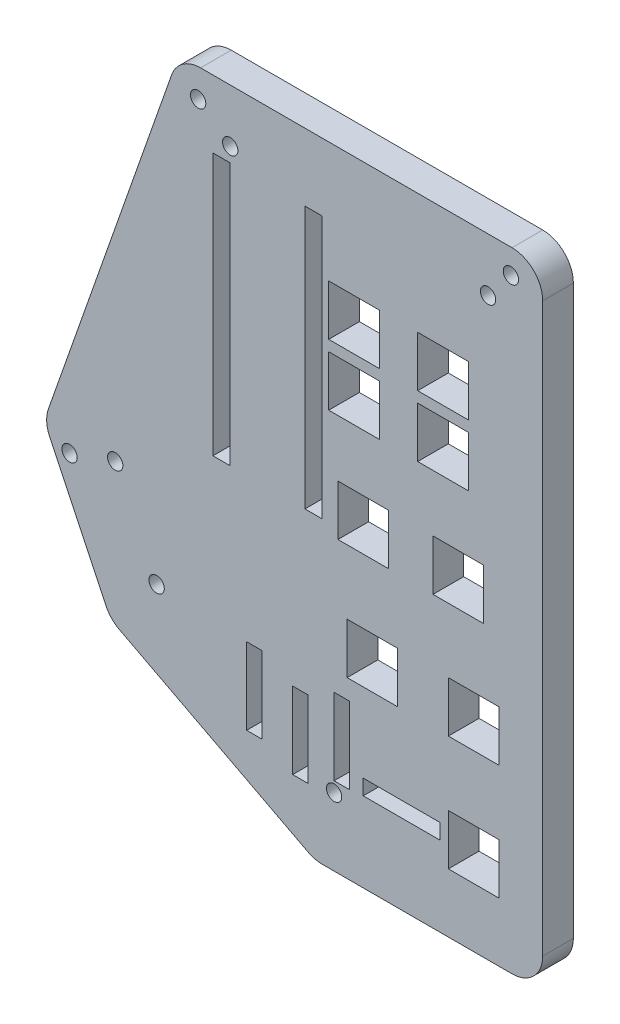
SolidWorks part; units mm, degrees
ref_plane "Front Plane" through (0, 0, 0) normal (0, 0, 1) x (1, 0, 0)
ref_plane "Top Plane" through (0, 0, 0) normal (0, 1, 0) x (1, 0, 0)
ref_plane "Right Plane" through (0, 0, 0) normal (1, 0, 0) x (0, 0, -1)
sketch "Sketch1" plane through (0, 0, 0) normal (0, 0, 1) x (1, 0, 0)
  line L6 (-20.066, -57.15) -> (46.99, -57.15) construction
  line L7 (-12.446, -73.152) -> (46.99, -73.152) construction
  line L8 (-3.3141, 6.35) -> (48.26, 6.35)
  line L9 (53.34, 1.27) -> (53.34, -92.71)
  line L10 (48.26, -97.79) -> (16.847, -97.79)
  line L16 (-8.1072, 2.9529) -> (-28.5162, -55.1739)
  line L18 (-20.066, -57.15) -> (-29.21, -57.15) construction
  line L26 (0, 0) -> (46.99, 0) construction
  line L27 (46.99, 0) -> (46.99, -88.9) construction
  line L28 (46.99, -88.9) -> (17.78, -88.9) construction
  line L29 (17.78, -88.9) -> (-12.446, -73.152) construction
  line L30 (-12.446, -73.152) -> (-20.066, -57.15) construction
  line L31 (-20.066, -57.15) -> (0, 0) construction
  line L32 (46.99, -57.15) -> (46.99, -88.9) construction
  line L33 (17.78, -88.9) -> (15.603, -97.79) construction
  line L34 (-12.446, -73.152) -> (-17.9301, -78.4424) construction
  line L35 (14.4997, -97.2152) -> (-16.7505, -80.9336)
  line L36 (-28.3096, -59.0409) -> (-18.9898, -78.6124)
  arc A0 (14.4997, -97.2152) -> (16.847, -97.79) centre (16.847, -92.71) ccw
  arc A1 (-28.5162, -55.1739) -> (-28.3096, -59.0409) centre (-23.723, -56.8568) ccw
  arc A2 (-16.7505, -80.9336) -> (-18.9898, -78.6124) centre (-14.4033, -76.4284) cw
  arc A3 (53.34, -92.71) -> (48.26, -97.79) centre (48.26, -92.71) cw
  arc A4 (48.26, 6.35) -> (53.34, 1.27) centre (48.26, 1.27) cw
  arc A5 (-8.1072, 2.9529) -> (-3.3141, 6.35) centre (-3.3141, 1.27) cw
  circle A6 centre (48.0822, 2.286) radius 1.27
  circle A7 centre (-3.7187, 1.651) radius 1.27
  circle A8 centre (-25.0123, -59.762) radius 1.27
  point P25 (53.34, -97.79)
  point P28 (53.34, 6.35)
  dimension "D11" = 5.2578
  dimension "D8" = 5.08
  dimension "D9" = 2.54
  dimension "D1" = 88.9
  dimension "D2" = 29.21
  dimension "D3" = 59.436
  dimension "D4" = 67.056
  dimension "D5" = 104.14
  dimension "D6" = 82.55
  dimension "D7" = 46.99
  dimension "D10" = 4.064
  dimension "D12" = 4.699
  dimension "D13" = 103.76
  dimension "D14" = 4.572
  dimension "D15" = 4.826
  dimension "D16" = 2.667
  dimension "D17" = 108.51
extrude "Boss-Extrude1" add sketch "Sketch1" along normal blind 5.08
sketch "Sketch3" plane through (0, 0, 5.08) normal (0, 0, 1) x (1, 0, 0)
  line L0 (46.99, -88.9) -> (0, -88.9) construction
  line L6 (-20.066, -57.15) -> (46.99, -57.15) construction
  line L7 (-12.446, -73.152) -> (46.99, -73.152) construction
  line L8 (0, 0) -> (46.99, 0) construction
  line L9 (46.99, 0) -> (46.99, -88.9) construction
  line L10 (46.99, -88.9) -> (17.78, -88.9) construction
  line L11 (17.78, -88.9) -> (-12.446, -73.152) construction
  line L12 (-12.446, -73.152) -> (-20.066, -57.15) construction
  line L13 (-20.066, -57.15) -> (0, 0) construction
sketch "Sketch5" plane through (0, 0, 0) normal (0, 0, -1) x (-1, 0, 0)
  line L0 (-46.99, 0) -> (-46.99, -17.78) construction
  line L1 (-46.99, 0) -> (-1.524, 0) construction
  line L2 (-46.99, -17.78) -> (-36.83, -17.78) construction
  line L3 (-46.99, 0) -> (-46.99, -27.94) construction
  line L8 (-41.021, -13.589) -> (-32.639, -13.589)
  line L9 (-41.021, -13.589) -> (-41.021, -21.971)
  line L10 (-46.99, 0) -> (-46.99, -45.72) construction
  line L15 (-41.021, -21.971) -> (-32.639, -21.971)
  line L16 (-32.639, -13.589) -> (-32.639, -21.971)
  line L17 (-46.99, 0) -> (-46.99, -88.9) construction
  line L18 (-46.99, -45.72) -> (-39.37, -45.72) construction
  line L19 (-41.021, -13.589) -> (-32.639, -21.971) construction
  line L20 (-46.99, 0) -> (-46.99, -64.77) construction
  line L21 (-43.561, -41.529) -> (-35.179, -41.529)
  line L22 (-43.561, -41.529) -> (-43.561, -49.911)
  line L23 (-43.561, -49.911) -> (-35.179, -49.911)
  line L24 (-35.179, -41.529) -> (-35.179, -49.911)
  line L25 (-43.561, -41.529) -> (-35.179, -49.911) construction
  line L26 (-43.561, -49.911) -> (-35.179, -41.529) construction
  line L27 (-46.99, -64.77) -> (-41.91, -64.77) construction
  line L28 (-41.021, -21.971) -> (-32.639, -13.589) construction
  line L29 (-46.99, -27.94) -> (-36.83, -27.94) construction
  line L30 (-46.99, 0) -> (-46.99, -83.82) construction
  line L31 (-41.021, -23.749) -> (-32.639, -23.749)
  line L32 (-41.021, -23.749) -> (-41.021, -32.131)
  line L33 (-41.021, -32.131) -> (-32.639, -32.131)
  line L34 (-32.639, -23.749) -> (-32.639, -32.131)
  line L35 (-41.021, -23.749) -> (-32.639, -32.131) construction
  line L36 (-41.021, -32.131) -> (-32.639, -23.749) construction
  line L37 (-46.101, -60.579) -> (-37.719, -60.579)
  line L38 (-46.101, -60.579) -> (-46.101, -68.961)
  line L39 (-46.101, -68.961) -> (-37.719, -68.961)
  line L40 (-37.719, -60.579) -> (-37.719, -68.961)
  line L41 (-46.101, -60.579) -> (-37.719, -68.961) construction
  line L42 (-46.101, -68.961) -> (-37.719, -60.579) construction
  line L43 (-46.99, -83.82) -> (-41.91, -83.82) construction
  line L44 (-36.83, -17.78) -> (-22.098, -17.78) construction
  line L45 (-46.101, -79.629) -> (-37.719, -79.629)
  line L46 (-46.101, -79.629) -> (-46.101, -88.011)
  line L47 (-46.101, -88.011) -> (-37.719, -88.011)
  line L48 (-37.719, -79.629) -> (-37.719, -88.011)
  line L49 (-46.101, -79.629) -> (-37.719, -88.011) construction
  line L50 (-46.101, -88.011) -> (-37.719, -79.629) construction
  line L51 (-36.83, -27.94) -> (-22.098, -27.94) construction
  line L52 (-39.37, -45.72) -> (-23.622, -45.72) construction
  line L53 (-41.91, -64.77) -> (-25.146, -64.77) construction
  line L54 (-46.99, 0) -> (-16.764, 0) construction
  line L55 (-26.289, -13.589) -> (-17.907, -13.589)
  line L56 (-26.289, -13.589) -> (-26.289, -21.971)
  line L57 (-26.289, -21.971) -> (-17.907, -21.971)
  line L58 (-17.907, -13.589) -> (-17.907, -21.971)
  line L59 (-26.289, -13.589) -> (-17.907, -21.971) construction
  line L60 (-26.289, -21.971) -> (-17.907, -13.589) construction
  line L61 (-26.289, -23.749) -> (-17.907, -23.749)
  line L62 (-26.289, -23.749) -> (-26.289, -32.131)
  line L63 (-26.289, -32.131) -> (-17.907, -32.131)
  line L64 (-17.907, -23.749) -> (-17.907, -32.131)
  line L65 (-26.289, -23.749) -> (-17.907, -32.131) construction
  line L66 (-26.289, -32.131) -> (-17.907, -23.749) construction
  line L67 (-27.813, -41.529) -> (-19.431, -41.529)
  line L68 (-27.813, -41.529) -> (-27.813, -49.911)
  line L69 (-27.813, -49.911) -> (-19.431, -49.911)
  line L70 (-19.431, -41.529) -> (-19.431, -49.911)
  line L71 (-27.813, -41.529) -> (-19.431, -49.911) construction
  line L72 (-27.813, -49.911) -> (-19.431, -41.529) construction
  line L73 (-29.337, -60.579) -> (-20.955, -60.579)
  line L74 (-29.337, -60.579) -> (-29.337, -68.961)
  line L75 (-29.337, -68.961) -> (-20.955, -68.961)
  line L76 (-20.955, -60.579) -> (-20.955, -68.961)
  line L77 (-29.337, -60.579) -> (-20.955, -68.961) construction
  line L78 (-29.337, -68.961) -> (-20.955, -60.579) construction
  line L79 (0, 0) -> (-46.99, 0) construction
  line L80 (-16.764, 0) -> (-16.764, -4.826) construction
  line L81 (-46.99, 0) -> (-13.97, 0) construction
  line L82 (-13.97, 0) -> (-13.97, -4.826) construction
  line L83 (-1.524, 0) -> (-1.524, -4.826) construction
  line L84 (-46.99, 0) -> (-17.1256, 0) construction
  line L85 (-1.524, 0) -> (-1.524, -48.26) construction
  line L86 (-46.99, 0) -> (1.27, 0) construction
  line L87 (1.27, 0) -> (1.27, -4.826) construction
  line L88 (-16.764, 0) -> (-16.764, -48.26) construction
  line L90 (-16.764, -4.826) -> (-13.97, -4.826)
  line L91 (-16.764, -4.826) -> (-16.764, -48.26)
  line L92 (-16.764, -48.26) -> (-13.97, -48.26)
  line L93 (-13.97, -4.826) -> (-13.97, -48.26)
  line L94 (-1.524, -4.826) -> (1.27, -4.826)
  line L95 (-1.524, -4.826) -> (-1.524, -48.26)
  line L96 (-1.524, -48.26) -> (1.27, -48.26)
  line L97 (1.27, -4.826) -> (1.27, -48.26)
  dimension "D2" = 8.382
  dimension "D3" = 64.77
  dimension "D4" = 8.382
  dimension "D5" = 10.16
  dimension "D6" = 17.78
  dimension "D7" = 8.382
  dimension "D8" = 8.382
  dimension "D9" = 45.72
  dimension "D10" = 7.62
  dimension "D11" = 8.382
  dimension "D12" = 8.382
  dimension "D13" = 27.94
  dimension "D14" = 10.16
  dimension "D15" = 5.08
  dimension "D16" = 8.382
  dimension "D17" = 8.382
  dimension "D18" = 8.382
  dimension "D19" = 8.382
  dimension "D20" = 83.82
  dimension "D21" = 5.08
  dimension "D22" = 8.382
  dimension "D23" = 8.382
  dimension "D24" = 14.732
  dimension "D25" = 8.382
  dimension "D26" = 8.382
  dimension "D27" = 14.732
  dimension "D28" = 8.382
  dimension "D29" = 8.382
  dimension "D30" = 15.748
  dimension "D31" = 8.382
  dimension "D32" = 8.382
  dimension "D33" = 16.764
  dimension "D34" = 30.226
  dimension "D35" = 4.826
  dimension "D36" = 33.02
  dimension "D37" = 4.826
  dimension "D38" = 45.466
  dimension "D39" = 4.826
  dimension "D40" = 48.26
  dimension "D41" = 4.826
  dimension "D42" = 48.26
  dimension "D43" = 48.26
extrude "Cut-Extrude1" cut sketch "Sketch5" against normal through all
sketch "Sketch7" plane through (0, 0, 5.08) normal (0, 0, 1) x (1, 0, 0)
  line L0 (46.99, 0) -> (44.2976, 0) construction
  line L1 (0, 0) -> (46.99, 0) construction
  line L2 (44.2976, 0) -> (44.2976, -2.4892) construction
  line L3 (46.99, 0) -> (1.6002, 0) construction
  line L4 (1.6002, 0) -> (1.6002, -2.4384) construction
  line L5 (-20.066, -57.15) -> (-17.4498, -57.15) construction
  line L6 (-20.066, -57.15) -> (46.99, -57.15) construction
  line L7 (-12.446, -73.152) -> (-10.5918, -73.152) construction
  line L8 (-12.446, -73.152) -> (46.99, -73.152) construction
  line L9 (-10.5918, -73.152) -> (-10.5918, -71.3486) construction
  line L10 (17.78, -88.9) -> (17.78, -86.5378) construction
  line L11 (17.78, -86.5378) -> (18.796, -86.5378) construction
  circle A0 centre (44.2976, -2.4892) radius 1.27
  circle A1 centre (1.6002, -2.4384) radius 1.27
  circle A2 centre (-17.4498, -57.15) radius 1.27
  circle A3 centre (-10.5918, -71.3486) radius 1.27
  circle A4 centre (18.796, -86.5378) radius 1.27
  dimension "D3" = 2.54
  dimension "D6" = 2.54
  dimension "D8" = 2.54
  dimension "D11" = 2.54
  dimension "D14" = 2.54
  dimension "D1" = 2.6924
  dimension "D2" = 2.4892
  dimension "D4" = 45.3898
  dimension "D5" = 2.4384
  dimension "D7" = 2.6162
  dimension "D9" = 1.8542
  dimension "D10" = 1.8034
  dimension "D12" = 2.3622
  dimension "D13" = 1.016
extrude "Cut-Extrude3" cut sketch "Sketch7" against normal through all
sketch "Sketch8" plane through (0, 0, 5.08) normal (0, 0, 1) x (1, 0, 0)
  line L0 (23.622, -82.042) -> (36.322, -82.042)
  line L1 (23.622, -82.042) -> (23.622, -84.582)
  line L2 (23.622, -84.582) -> (36.322, -84.582)
  line L3 (36.322, -82.042) -> (36.322, -84.582)
  line L4 (18.796, -72.136) -> (21.336, -72.136)
  line L5 (18.796, -72.136) -> (18.796, -84.836)
  line L6 (18.796, -84.836) -> (21.336, -84.836)
  line L7 (21.336, -72.136) -> (21.336, -84.836)
  line L8 (11.938, -74.676) -> (14.478, -74.676)
  line L9 (11.938, -74.676) -> (11.938, -87.376)
  line L10 (11.938, -87.376) -> (14.478, -87.376)
  line L11 (14.478, -74.676) -> (14.478, -87.376)
  line L12 (4.318, -72.136) -> (6.858, -72.136)
  line L13 (4.318, -72.136) -> (4.318, -84.836)
  line L14 (4.318, -84.836) -> (6.858, -84.836)
  line L15 (6.858, -72.136) -> (6.858, -84.836)
  line L16 (46.99, -83.312) -> (36.322, -83.312) construction
  line L17 (46.99, 0) -> (46.99, -88.9) construction
  line L18 (36.322, -83.312) -> (36.322, 0) construction
  line L19 (0, 0) -> (46.99, 0) construction
  line L20 (21.336, -72.136) -> (46.99, -72.136) construction
  line L21 (21.336, -72.136) -> (21.336, 0) construction
  line L22 (6.858, -72.136) -> (46.99, -72.136) construction
  line L23 (14.478, -74.676) -> (46.99, -74.676) construction
  line L24 (14.478, -74.676) -> (14.478, 0) construction
  line L25 (6.858, -72.136) -> (6.858, 0) construction
  dimension "D1" = 12.7
  dimension "D2" = 2.54
  dimension "D3" = 12.7
  dimension "D4" = 2.54
  dimension "D5" = 12.7
  dimension "D6" = 2.54
  dimension "D7" = 12.7
  dimension "D8" = 2.54
  dimension "D9" = 10.668
  dimension "D10" = 83.312
  dimension "D11" = 25.654
  dimension "D12" = 72.136
  dimension "D13" = 32.512
  dimension "D14" = 74.676
  dimension "D15" = 40.132
  dimension "D16" = 72.136
extrude "Cut-Extrude4" cut sketch "Sketch8" against normal through all
